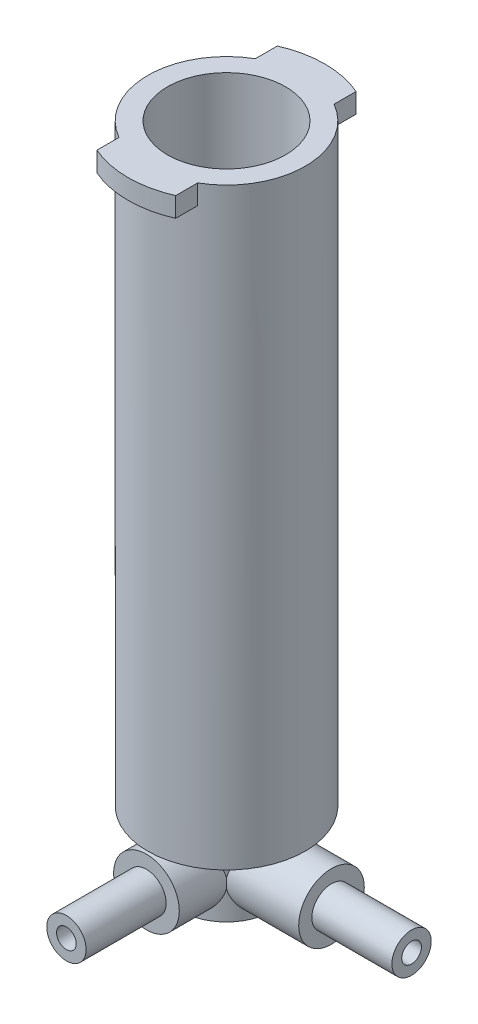
SolidWorks part; units mm, degrees
ref_plane "Front Plane" through (0, 0, 0) normal (0, 0, 1) x (1, 0, 0)
ref_plane "Top Plane" through (0, 0, 0) normal (0, 1, 0) x (1, 0, 0)
ref_plane "Right Plane" through (0, 0, 0) normal (1, 0, 0) x (0, 0, -1)
sketch "Sketch1" plane through (0, 0, 0) normal (0, 1, 0) x (1, 0, 0)
  circle A0 centre (0, 0) radius 6
extrude "Boss-Extrude1" add sketch "Sketch1" along normal blind 45.2 contours A0
shell "Shell1" thickness 1.5 removed face at (0, 45.2, 6)
sketch "Sketch2" plane through (0, 0, 0) normal (0, -1, 0) x (1, 0, 0)
  circle A0 centre (0, 0) radius 3.5
extrude "Boss-Extrude2" add sketch "Sketch2" along normal blind 5.2
shell "Shell2" thickness 1.5 removed face at (0, 1.5, 4.5)
sketch "Sketch3" plane through (0, 0, 0) normal (0, 0, 1) x (1, 0, 0)
  circle A0 centre (0, -2.6442) radius 2.5
  point P2 (0, -2.6442)
extrude "Boss-Extrude3" add sketch "Sketch3" along normal blind 6.1
sketch "Sketch4" plane through (0, 0, 6.1) normal (0, 0, 1) x (1, 0, 0)
  circle A0 centre (0, -2.6442) radius 1.5
extrude "Boss-Extrude4" add sketch "Sketch4" along normal blind 6.1
sketch "Sketch5" plane through (0, 0, 12.2) normal (0, 0, 1) x (1, 0, 0)
  circle A0 centre (0, -2.6442) radius 0.75
extrude "Cut-Extrude1" cut sketch "Sketch5" against normal blind 12.1
sketch "Sketch6" plane through (0, -3.7, 0) normal (0, 1, 0) x (1, 0, 0)
  line L0 (2, 0) -> (-2, 0) construction
  circle A0 centre (0, 0) radius 2
extrude "Cut-Extrude2" cut sketch "Sketch6" along normal blind 12.1
sketch "Sketch7" plane through (0, 0, 0) normal (1, 0, 0) x (0, 0, -1)
  line L0 (0, 2.3996) -> (0, -6.384) construction
  line L1 (-6.1, -2.6442) -> (5.6134, -2.6442) construction
  line L2 (-6.1, -1.1442) -> (-6.1, -4.1442) construction
  circle A0 centre (0, -2.6442) radius 2.5
extrude "Boss-Extrude5" add sketch "Sketch7" along normal blind 8
sketch "Sketch8" plane through (8, 0, 0) normal (1, 0, 0) x (0, 0, -1)
  circle A0 centre (0, -2.6442) radius 1.5
extrude "Boss-Extrude6" add sketch "Sketch8" along normal blind 6.1
sketch "Sketch9" plane through (14.1, 0, 0) normal (1, 0, 0) x (0, 0, -1)
  circle A0 centre (0, -2.6442) radius 0.75
extrude "Cut-Extrude3" cut sketch "Sketch9" against normal blind 14.1
sketch "Sketch10" plane through (0, -3.7, 0) normal (0, 1, 0) x (1, 0, 0)
  circle A0 centre (0, 0) radius 2
extrude "Cut-Extrude4" cut sketch "Sketch10" along normal blind 14.1
sketch "Sketch11" plane through (0, 45.2, 0) normal (0, 1, 0) x (1, 0, 0)
  line L1 (3, -5.1962) -> (3, -6.8739)
  line L3 (-3, -5.1962) -> (-3, -6.8739)
  line L4 (-3, 5.1962) -> (-3, 6.8739)
  line L5 (3, 5.1962) -> (3, 6.8739)
  arc A0 (-3, -6.8739) -> (3, -6.8739) centre (0, 0) ccw
  arc A1 (-3, -5.1962) -> (3, -5.1962) centre (0, 0) ccw
  arc A2 (-3, 6.8739) -> (3, 6.8739) centre (0, 0) cw
  arc A3 (-3, 5.1962) -> (3, 5.1962) centre (0, 0) cw
extrude "Boss-Extrude7" add sketch "Sketch11" against normal blind 1.5
